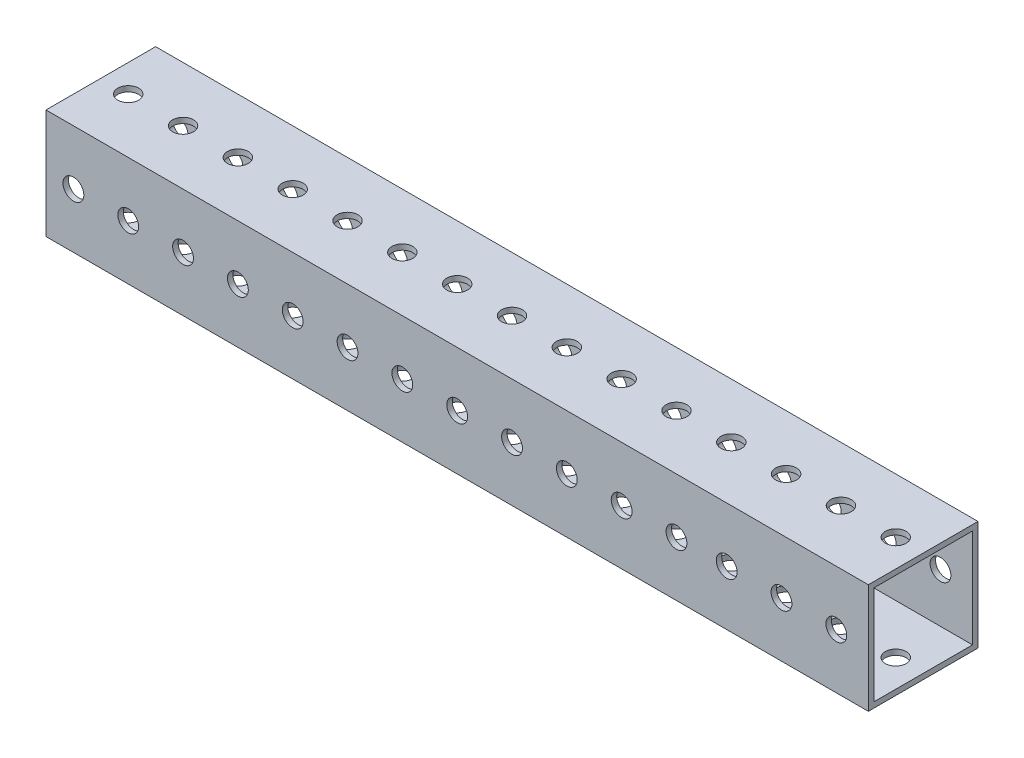
SolidWorks part; units mm, degrees
ref_plane "Front Plane" through (0, 0, 0) normal (0, 0, 1) x (1, 0, 0)
ref_plane "Top Plane" through (0, 0, 0) normal (0, 1, 0) x (1, 0, 0)
ref_plane "Right Plane" through (0, 0, 0) normal (1, 0, 0) x (0, 0, -1)
sketch "Sketch1" plane through (0, 0, 0) normal (0, 1, 0) x (1, 0, 0)
  line L1 (0, 0) -> (190.5, 0)
  line L2 (0, 0) -> (0, 25.4)
  line L3 (0, 25.4) -> (190.5, 25.4)
  line L4 (190.5, 0) -> (190.5, 25.4)
  dimension "D1" = 25.4
  dimension "D2" = 190.5
extrude "Boss-Extrude1" add sketch "Sketch1" along normal blind 25.4
sketch "Sketch2" plane through (0, 0, 0) normal (-1, 0, 0) x (0, 0, 1)
  line L0 (-25.4, 25.4) -> (0, 25.4) construction
  line L1 (-25.4, 0) -> (0, 0) construction
  line L2 (-25.4, 25.4) -> (-25.4, 0) construction
  line L3 (-24.13, 1.27) -> (-1.27, 1.27)
  line L4 (-24.13, 1.27) -> (-24.13, 24.13)
  line L5 (-24.13, 24.13) -> (-1.27, 24.13)
  line L6 (-1.27, 1.27) -> (-1.27, 24.13)
  point P8 (-12.7, 12.7)
  dimension "D1" = 1.27
  dimension "D2" = 1.27
  dimension "D3" = 1.27
extrude "Cut-Extrude1" cut sketch "Sketch2" against normal through all
sketch "Sketch3" plane through (0, 25.4, 0) normal (0, 1, 0) x (1, 0, 0)
  line L0 (190.5, 25.4) -> (0, 25.4) construction
  line L1 (0, 25.4) -> (0, 0) construction
  circle A0 centre (6.35, 12.7) radius 2.413
  circle A1 centre (19.05, 12.7) radius 2.413
  circle A2 centre (31.75, 12.7) radius 2.413
  circle A3 centre (44.45, 12.7) radius 2.413
  circle A4 centre (57.15, 12.7) radius 2.413
  circle A5 centre (69.85, 12.7) radius 2.413
  circle A6 centre (82.55, 12.7) radius 2.413
  circle A7 centre (95.25, 12.7) radius 2.413
  circle A8 centre (107.95, 12.7) radius 2.413
  circle A9 centre (120.65, 12.7) radius 2.413
  circle A10 centre (133.35, 12.7) radius 2.413
  circle A11 centre (146.05, 12.7) radius 2.413
  circle A12 centre (158.75, 12.7) radius 2.413
  circle A13 centre (171.45, 12.7) radius 2.413
  circle A14 centre (184.15, 12.7) radius 2.413
  circle A15 centre (196.85, 12.7) radius 2.413
  dimension "D1" = 12.7
  dimension "D2" = 6.35
  dimension "D3" = 4.826
  dimension "D4" = 14
  dimension "D5" = 3
extrude "Cut-Extrude2" cut sketch "Sketch3" against normal through all
sketch "Sketch4" plane through (0, 0, -25.4) normal (0, 0, -1) x (-1, 0, 0)
  line L0 (-190.5, 0) -> (0, 0) construction
  line L1 (0, 25.4) -> (0, 0) construction
  line L2 (-190.5, 25.4) -> (-190.5, 0) construction
  circle A0 centre (-6.35, 12.7) radius 2.413
  circle A1 centre (-19.05, 12.7) radius 2.413
  circle A2 centre (-31.75, 12.7) radius 2.413
  circle A3 centre (-44.45, 12.7) radius 2.413
  circle A4 centre (-57.15, 12.7) radius 2.413
  circle A5 centre (-69.85, 12.7) radius 2.413
  circle A6 centre (-82.55, 12.7) radius 2.413
  circle A7 centre (-95.25, 12.7) radius 2.413
  circle A8 centre (-107.95, 12.7) radius 2.413
  circle A9 centre (-120.65, 12.7) radius 2.413
  circle A10 centre (-133.35, 12.7) radius 2.413
  circle A11 centre (-146.05, 12.7) radius 2.413
  circle A12 centre (-157.6781, 12.7) radius 2.413
  circle A13 centre (-170.3781, 12.7) radius 2.413
  circle A14 centre (-183.0781, 12.7) radius 2.413
  circle A15 centre (-196.85, 12.7) radius 2.413
  dimension "D1" = 4.826
  dimension "D2" = 12.7
  dimension "D3" = 6.35
  dimension "D4" = 12.7
  dimension "D5" = 12.7
  dimension "D6" = 7.4219
extrude "Cut-Extrude3" cut sketch "Sketch4" against normal through all
